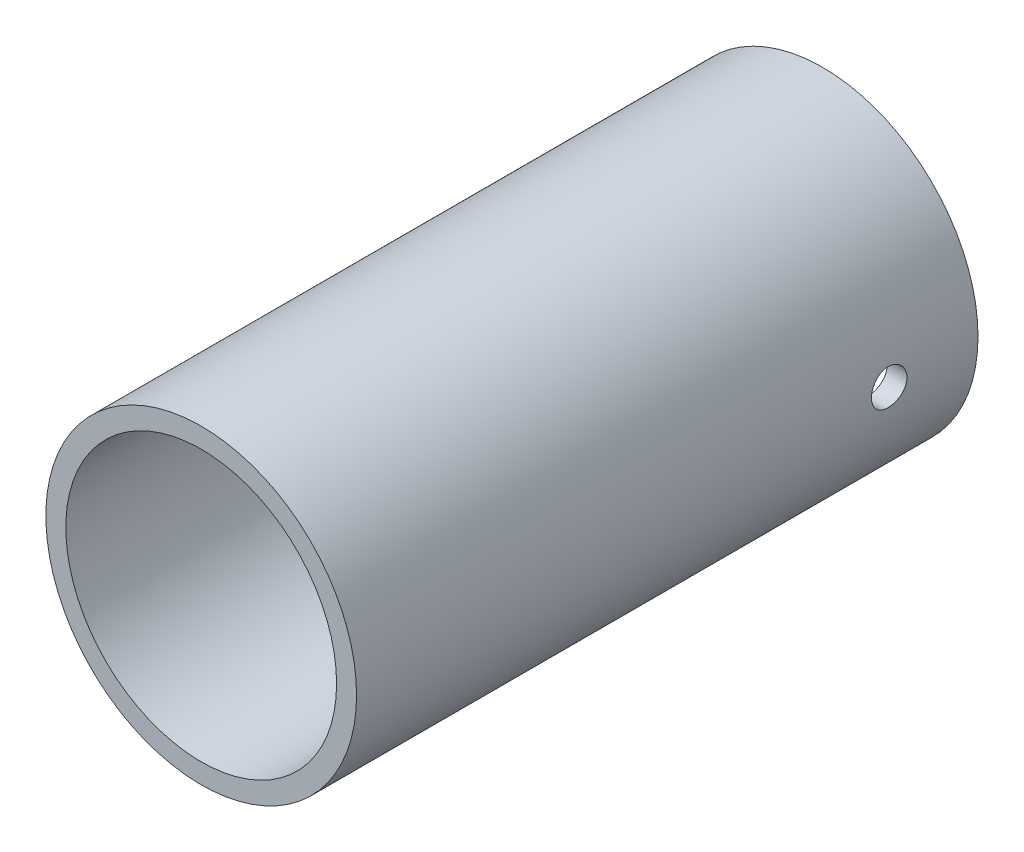
SolidWorks part; units mm, degrees
ref_plane "Front Plane" through (0, 0, 0) normal (0, 0, 1) x (1, 0, 0)
ref_plane "Top Plane" through (0, 0, 0) normal (0, 1, 0) x (1, 0, 0)
ref_plane "Right Plane" through (0, 0, 0) normal (1, 0, 0) x (0, 0, -1)
sketch "Sketch1" plane through (0, 0, 0) normal (0, 0, 1) x (1, 0, 0)
  line L0 (3.5, 0) -> (3.05, 0) construction
  line L1 (-3.5, 0) -> (3.5, 0) construction
  dimension "OD" = 7
  dimension "Wall Thickness" = 0.45
sketch "Sketch2" plane through (0, 0, 0) normal (1, 0, 0) x (0, 0, -1)
  line L0 (7, 0) -> (-7, 0)
  point P4 (0, 0)
  dimension "Length" = 14
sketch "Sketch3" plane through (0, 0, 0) normal (0, 0, 1) x (1, 0, 0)
  circle A0 centre (0, 0) radius 3.5
  circle A1 centre (0, 0) radius 3.05
extrude "Boss-Extrude1" add sketch "Sketch3" along normal up to vertex (7 mm away) and the other way up to vertex (7 mm away) up to point (0, 0, 7) other way up to point (0, 0, -7)
ref_plane "Plane1" through (3.55, 0, 0) normal (1, 0, 0) x (0, 0, -1)
sketch "Sketch4" plane through (3.55, 0, 0) normal (1, 0, 0) x (0, 0, -1)
  line L0 (-7, 0) -> (7, 0) construction
  line L1 (7, -3.5) -> (7, 3.5) construction
  circle A0 centre (5, 0) radius 0.4
  dimension "D1" = 2
extrude "Cut-Extrude1" cut sketch "Sketch4" against normal through all
